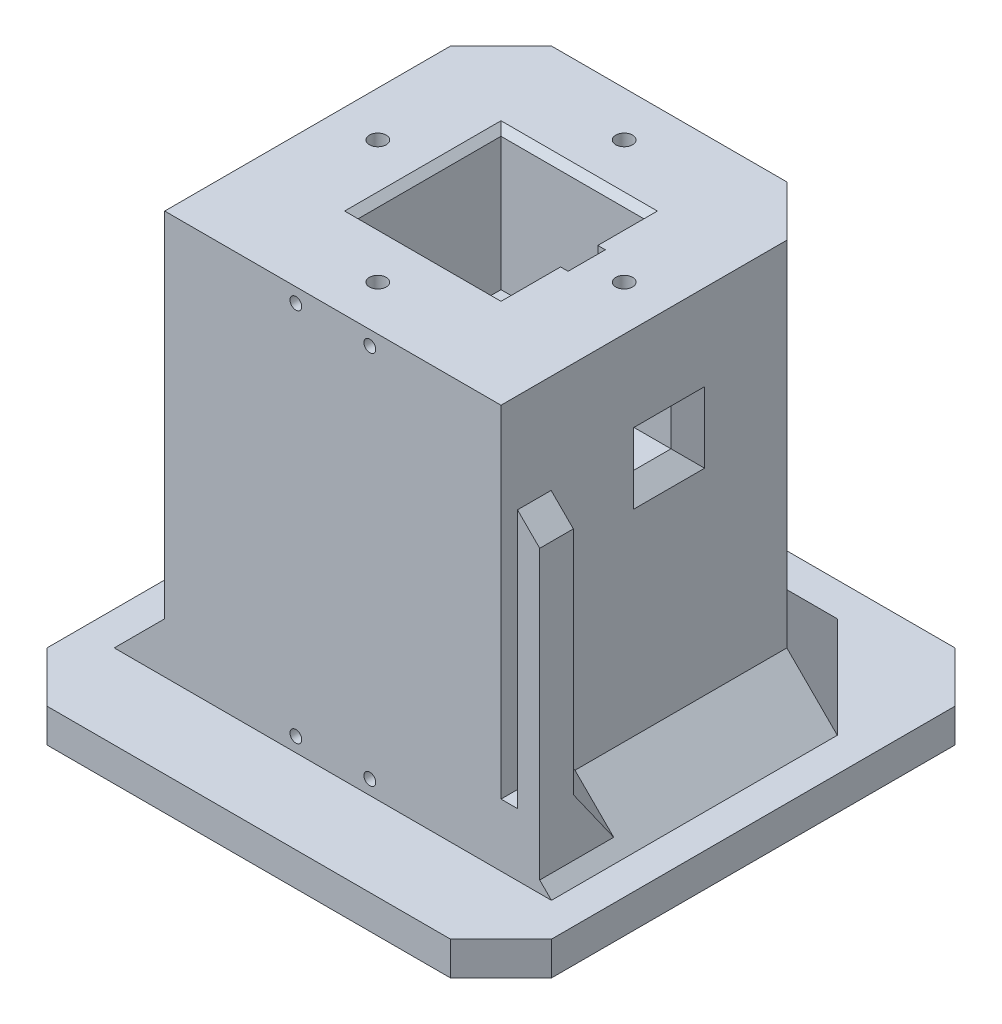
SolidWorks part; units mm, degrees
ref_plane "Front Plane" through (0, 0, 0) normal (0, 0, 1) x (1, 0, 0)
ref_plane "Top Plane" through (0, 0, 0) normal (0, 1, 0) x (1, 0, 0)
ref_plane "Right Plane" through (0, 0, 0) normal (1, 0, 0) x (0, 0, -1)
sketch "Sketch1" plane through (0, 0, 0) normal (0, 1, 0) x (1, 0, 0)
  line L1 (-75, 75) -> (75, 75)
  line L2 (-75, 75) -> (-75, -75)
  line L3 (-75, -75) -> (75, -75)
  line L4 (75, 75) -> (75, -75)
  line L5 (-75, 75) -> (75, -75) construction
  line L6 (-75, -75) -> (75, 75) construction
  point P0 (0, 0)
  dimension "D1" = 150
extrude "Boss-Extrude1" add sketch "Sketch1" along normal blind 10
sketch "Sketch2" plane through (0, 10, 0) normal (0, 1, 0) x (1, 0, 0)
  line L1 (-50, 50) -> (50, 50)
  line L2 (-50, 50) -> (-50, -50)
  line L3 (-50, -50) -> (50, -50)
  line L4 (50, 50) -> (50, -50)
  line L5 (-50, 50) -> (50, -50) construction
  line L6 (-50, -50) -> (50, 50) construction
  point P0 (0, 0)
  dimension "D1" = 100
extrude "Boss-Extrude2" add sketch "Sketch2" along normal blind 120
sketch "Sketch3" plane through (0, 130, 0) normal (0, 1, 0) x (1, 0, 0)
  line L1 (-21.25, 21.25) -> (21.25, 21.25)
  line L2 (-21.25, 21.25) -> (-21.25, -21.25)
  line L3 (-21.25, -21.25) -> (21.25, -21.25)
  line L4 (21.25, 21.25) -> (21.25, -21.25)
  line L5 (-21.25, 21.25) -> (21.25, -21.25) construction
  line L6 (-21.25, -21.25) -> (21.25, 21.25) construction
  point P0 (0, 0)
  dimension "D1" = 42.5
extrude "Cut-Extrude1" cut sketch "Sketch3" against normal blind 41.5
chamfer "Chamfer1" distance 15 angle 45 4 edges at (75, 5, -75) (-75, 5, -75) (-75, 5, 75) (75, 5, 75)
chamfer "Chamfer2" distance 15 angle 45 5 edges at (50, 70, -50) (-50, 70, -50) (-50, 10, 0) (0, 10, -50) (50, 10, 0)
sketch "Sketch4" plane through (0, 130, 0) normal (0, 1, 0) x (1, 0, 0)
  line L0 (21.25, 5.5457) -> (25.4924, 5.5457)
  line L1 (21.25, -21.25) -> (21.25, 21.25) construction
  line L2 (25.4924, 5.5457) -> (25.4924, -5.5457)
  line L3 (25.4924, -5.5457) -> (21.25, -5.5457)
  line L4 (21.25, -21.25) -> (21.25, 21.25)
  line L5 (21.25, 0) -> (25.4924, 0) construction
  line M6 (21.25, 21.25) -> (21.25, -21.25)
extrude "Cut-Extrude2" cut sketch "Sketch4" against normal blind 41.5 contours L5 L4 L3 L2 | L5 L2 L0 M6 region at (23.3712, 130, -2.7729) region at (23.3712, 130, 2.7729)
sketch "Sketch5" plane through (25.4924, 0, 0) normal (-1, 0, 0) x (0, 0, 1)
  line L1 (5.5457, 88.5) -> (-5.5457, 88.5)
  line L2 (5.5457, 88.5) -> (5.5457, 99.5171)
  line L3 (5.5457, 99.5171) -> (-5.5457, 99.5171)
  line L4 (5.5457, 130) -> (-5.5457, 130)
  line L5 (-5.5457, 130) -> (-5.5457, 88.5)
  line L6 (-5.5457, 88.5) -> (5.5457, 88.5)
  line L7 (5.5457, 88.5) -> (5.5457, 130)
  line L8 (5.5457, 130) -> (-5.5457, 130)
  line L9 (-5.5457, 130) -> (-5.5457, 88.5)
  line L10 (-5.5457, 88.5) -> (5.5457, 88.5)
  line L11 (5.5457, 88.5) -> (5.5457, 130)
  line L12 (-5.5457, 88.5) -> (-5.5457, 99.5171)
  line M6 (-5.5457, 130) -> (-5.5457, 88.5)
  line M7 (-5.5457, 88.5) -> (5.5457, 88.5)
  line M8 (5.5457, 88.5) -> (5.5457, 130)
  dimension "D1" = 0
extrude "Cut-Extrude5" cut sketch "Sketch5" against normal up to surface (24.5076 mm away) contours L3 M8 M6 M7 region at (25.4924, 94.0085, 0) up to face at (50, 77.5, 7.5)
chamfer "Chamfer3" distance 5 angle 45 4 edges at (50, 94.0085, -5.5457) (50, 99.5171, 0) (50, 94.0085, 5.5457) (50, 88.5, 0)
chamfer "Chamfer4" distance 5 angle 45 1 edges at (25.4924, 99.5171, 0)
chamfer "Chamfer5" distance 2 angle 45 7 edges at (21.25, 109.25, -5.5457) (21.25, 130, -13.3979) (0, 130, -21.25) (-21.25, 130, 0) (0, 130, 21.25) (21.25, 130, 13.3979) (21.25, 109.25, 5.5457)
sketch "Sketch6" plane through (0, 0, 50) normal (0, 0, 1) x (1, 0, 0)
  line L0 (0, 130) -> (0, 0) construction
  line L1 (-50, 130) -> (50, 130) construction
  line L2 (-50, 130) -> (-50, 10) construction
  line L3 (-65, 10) -> (65, 10) construction
  line L4 (-50, 70) -> (50, 70) construction
  line L5 (50, 130) -> (50, 25) construction
  line L7 (-11, 14.25) -> (11, 14.25) construction
  line L8 (-11, 14.25) -> (-11, 125.75) construction
  line L9 (-11, 125.75) -> (11, 125.75) construction
  line L10 (11, 14.25) -> (11, 125.75) construction
  line L11 (-11, 14.25) -> (11, 125.75) construction
  line L12 (-11, 125.75) -> (11, 14.25) construction
  circle A0 centre (11, 125.75) radius 1.75
  circle A1 centre (-11, 125.75) radius 1.75
  circle A2 centre (11, 14.25) radius 1.75
  circle A3 centre (-11, 14.25) radius 1.75
  point P14 (0, 70)
  dimension "D1" = 3.5
  dimension "D2" = 22
  dimension "D3" = 111.5
extrude "Cut-Extrude6" cut sketch "Sketch6" against normal blind 10 contours A1 | A0 | A3 | A2 region at (11, 125.75, 50) region at (-11, 125.75, 50) region at (11, 14.25, 50) region at (-11, 14.25, 50)
sketch "Sketch7" plane through (0, 0, 50) normal (0, 0, 1) x (1, 0, 0)
  line L0 (50, 25) -> (54.909, 20.091)
  line L1 (65, 10) -> (50, 25) construction
  line L2 (54.909, 20.091) -> (54.909, 105.5147)
  line L3 (54.909, 105.5147) -> (61.5126, 98.9112)
  line L4 (61.5126, 98.9112) -> (61.5126, 13.4874)
  line L5 (54.909, 20.091) -> (61.5126, 13.4874)
  line M6 (65, 10) -> (50, 25)
extrude "Boss-Extrude3" add sketch "Sketch7" against normal blind 10 contours L4 L3 L2 M6 region at (58.2108, 59.5011, 50)
chamfer "Chamfer6" distance 12 angle 45 2 edges at (54.909, 20.091, 45) (58.2108, 16.7892, 40) first distance on face at (57.8554, 17.1446, 26.25)
sketch "Sketch8" plane through (0, 130, 0) normal (0, 1, 0) x (1, 0, 0)
  line L0 (0, -50) -> (0, 0) construction
  line L1 (-65, -50) -> (65, -50) construction
  line L2 (0, 0) -> (50, 0) construction
  line L3 (50, -50) -> (50, 35) construction
  line L4 (-36.625, 0) -> (-50, 0) construction
  line L5 (-36.625, -36.625) -> (36.625, -36.625) construction
  line L6 (-36.625, -36.625) -> (-36.625, 36.625) construction
  line L7 (-36.625, 36.625) -> (36.625, 36.625) construction
  line L8 (36.625, -36.625) -> (36.625, 36.625) construction
  line L9 (-36.625, -36.625) -> (36.625, 36.625) construction
  line L10 (-36.625, 36.625) -> (36.625, -36.625) construction
  line L11 (-50, 35) -> (-50, -50) construction
  circle A0 centre (0, 36.625) radius 2.5
  circle A1 centre (36.625, 0) radius 2.5
  circle A2 centre (0, -36.625) radius 2.5
  circle A3 centre (-36.625, 0) radius 2.5
  dimension "D2" = 5
  dimension "D1" = 13.375
extrude "Cut-Extrude7" cut sketch "Sketch8" against normal blind 10
